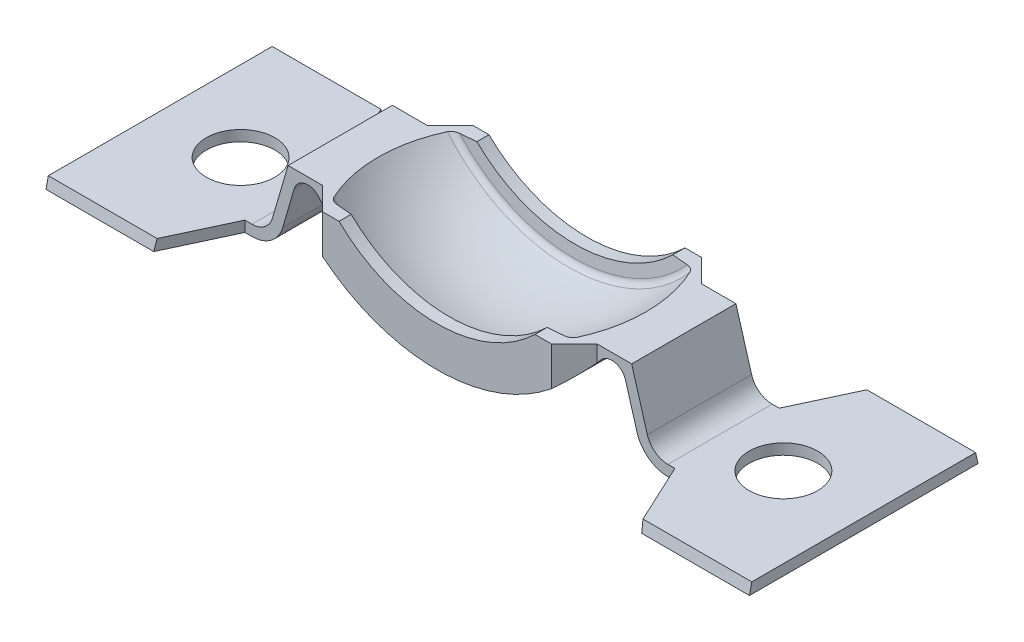
SolidWorks part; units mm, degrees
ref_plane "Alzado" through (0, 0, 0) normal (0, 0, 1) x (1, 0, 0)
ref_plane "Planta" through (0, 0, 0) normal (0, 1, 0) x (1, 0, 0)
ref_plane "Vista lateral" through (0, 0, 0) normal (1, 0, 0) x (0, 0, -1)
ref_plane "Plano1" through (0, 0, 0) normal (0, 0, 1) x (1, 0, 0)
sketch "Croquis1" plane through (0, 0, 0) normal (0, 0, 1) x (1, 0, 0)
  line L0 (-49.25, -23.8) -> (-49.25, -25.3)
  line L1 (-49.25, -25.3) -> (-29.1261, -25.3)
  line L2 (-24.8068, -22.0625) -> (-23.1945, -16.5466)
  line L3 (23.1945, -16.5466) -> (24.8068, -22.0625)
  line L4 (29.1261, -25.3) -> (49.25, -25.3)
  line L5 (49.25, -25.3) -> (49.25, -23.8)
  line L6 (49.25, -23.8) -> (29.1261, -23.8)
  line L7 (26.2465, -21.6417) -> (22.1857, -7.749)
  line L8 (-22.1857, -7.749) -> (-26.2465, -21.6417)
  line L9 (-29.1261, -23.8) -> (-49.25, -23.8)
  arc A0 (-29.1261, -25.3) -> (-24.8068, -22.0625) centre (-29.1261, -20.8) ccw
  arc A1 (-23.1945, -16.5466) -> (-19.7162, -15.8544) centre (-21.2748, -17.1077) cw
  arc A2 (-19.7162, -15.8544) -> (19.7162, -15.8544) centre (0, 0) ccw
  arc A3 (19.7162, -15.8544) -> (23.1945, -16.5466) centre (21.2748, -17.1077) cw
  arc A4 (24.8068, -22.0625) -> (29.1261, -25.3) centre (29.1261, -20.8) ccw
  arc A5 (29.1261, -23.8) -> (26.2465, -21.6417) centre (29.1261, -20.8) cw
  arc A6 (22.1857, -7.749) -> (-22.1857, -7.749) centre (0, 0) cw
  arc A7 (-26.2465, -21.6417) -> (-29.1261, -23.8) centre (-29.1261, -20.8) cw
extrude "Saliente-Extruir1" add sketch "Croquis1" against normal blind 16 and the other way blind 16
ref_plane "Plano2" through (0, 0, 0) normal (1, 0, 0) x (0, 0, -1)
sketch "Croquis2" plane through (0, 0, 0) normal (1, 0, 0) x (0, 0, -1)
  line L0 (-16, -25.3) -> (-10.5, 0)
  line L1 (-10.5, 0) -> (-10.5, 25.2)
  line L2 (-10.5, 25.2) -> (10.5, 25.2)
  line L3 (10.5, 25.2) -> (10.5, 0)
  line L4 (10.5, 0) -> (16, -25.3)
  line L5 (16, -25.3) -> (16, 26.2)
  line L6 (16, 26.2) -> (-16, 26.2)
  line L7 (-16, 26.2) -> (-16, -25.3)
extrude "Cortar-Extruir1" cut sketch "Croquis2" against normal blind 49.25 and the other way blind 49.25
ref_plane "Plano3" through (0, 0, 0) normal (0, 1, 0) x (1, 0, 0)
sketch "Croquis3" plane through (0, 0, 0) normal (0, 1, 0) x (1, 0, 0)
  circle A0 centre (38, 0) radius 4.8
extrude "Cortar-Extruir2" cut sketch "Croquis3" against normal blind 25.3
ref_plane "Plano4" through (0, 0, 0) normal (0, 1, 0) x (1, 0, 0)
sketch "Croquis4" plane through (0, 0, 0) normal (0, 1, 0) x (1, 0, 0)
  circle A0 centre (-38, 0) radius 4.8
extrude "Cortar-Extruir3" cut sketch "Croquis4" against normal blind 25.3
ref_plane "Plano5" through (0, 0, 0) normal (1, 0, 0) x (0, 0, -1)
sketch "Croquis5" plane through (0, 0, 0) normal (1, 0, 0) x (0, 0, -1)
  line L0 (-10.5, -19.7097) -> (-10.5, -23.65)
  line L1 (-10.5, -23.65) -> (10.5, -23.65)
  line L2 (10.5, -23.65) -> (10.5, -19.7097)
  line L3 (10.5, -19.7097) -> (8.8, -19.7097)
  line L4 (8.8, -19.7097) -> (8.6064, -21.2939)
  line L5 (-8.6064, -21.2939) -> (-8.8, -19.7097)
  line L6 (-8.8, -19.7097) -> (-10.5, -19.7097)
  line L7 (-16, 0) -> (16, 0) construction
  arc A0 (8.6064, -21.2939) -> (7.9522, -22.1136) centre (7.6138, -21.1726) cw
  arc A1 (7.9522, -22.1136) -> (-7.9522, -22.1136) centre (0, 0) cw
  arc A2 (-7.9522, -22.1136) -> (-8.6064, -21.2939) centre (-7.6138, -21.1726) cw
revolve "Revolución1" add sketch "Croquis5" angle 360 about L7 reverse direction yes
ref_plane "Plano6" through (0, 0, 0) normal (1, 0, 0) x (0, 0, -1)
sketch "Croquis6" plane through (0, 0, 0) normal (1, 0, 0) x (0, 0, -1)
  line L0 (-32, 36.35) -> (-32, -14.15)
  line L1 (-32, -14.15) -> (32, -14.15)
  line L2 (32, -14.15) -> (32, 36.35)
  line L3 (32, 36.35) -> (-32, 36.35)
extrude "Cortar-Extruir4" cut sketch "Croquis6" against normal blind 98.5 and the other way blind 98.5
ref_plane "Plano7" through (0, 0, 0) normal (0, 1, 0) x (1, 0, 0)
sketch "Croquis7" plane through (0, 0, 0) normal (0, 1, 0) x (1, 0, 0)
  line L0 (-59.25, -26) -> (59.25, -26)
  line L1 (59.25, -26) -> (59.25, 26)
  line L2 (59.25, 26) -> (-59.25, 26)
  line L3 (-59.25, 26) -> (-59.25, -26)
  line L4 (-49.25, 16) -> (-49.25, -16)
  line L5 (-49.25, -16) -> (-34.1647, -16)
  line L6 (-34.1647, -16) -> (-30.1078, -7.3)
  line L7 (-30.1078, -7.3) -> (-19.2, -7.3)
  line L8 (-19.2, -7.3) -> (-16, -10.5)
  line L9 (-16, -10.5) -> (16, -10.5)
  line L10 (16, -10.5) -> (19.2, -7.3)
  line L11 (19.2, -7.3) -> (30.1078, -7.3)
  line L12 (30.1078, -7.3) -> (34.1647, -16)
  line L13 (34.1647, -16) -> (49.25, -16)
  line L14 (49.25, -16) -> (49.25, 16)
  line L15 (49.25, 16) -> (34.1647, 16)
  line L16 (34.1647, 16) -> (30.1078, 7.3)
  line L17 (30.1078, 7.3) -> (19.2, 7.3)
  line L18 (19.2, 7.3) -> (16, 10.5)
  line L19 (16, 10.5) -> (-16, 10.5)
  line L20 (-16, 10.5) -> (-19.2, 7.3)
  line L21 (-19.2, 7.3) -> (-30.1078, 7.3)
  line L22 (-30.1078, 7.3) -> (-34.1647, 16)
  line L23 (-34.1647, 16) -> (-49.25, 16)
extrude "Cortar-Extruir5" cut sketch "Croquis7" against normal blind 25.3
